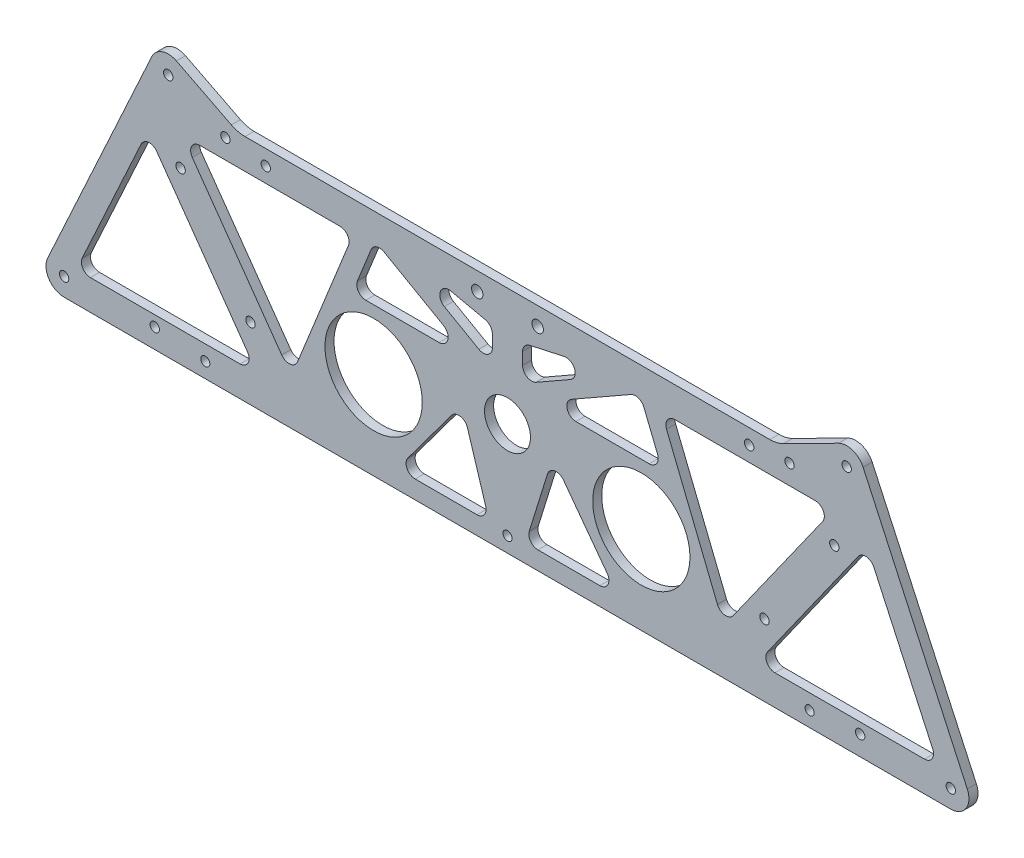
SolidWorks part; units mm, degrees
material "Hexcel AS4C (3000 丝)"
ref_plane "前视基准面" through (0, 0, 0) normal (0, 0, 1) x (1, 0, 0)
ref_plane "上视基准面" through (0, 0, 0) normal (0, 1, 0) x (1, 0, 0)
ref_plane "右视基准面" through (0, 0, 0) normal (1, 0, 0) x (0, 0, -1)
sketch "草图1" plane through (0, 0, 0) normal (0, 0, 1) x (1, 0, 0)
  line L0 (0, 0) -> (102.4311, 23.0839) construction
  line L1 (-1000, 0) -> (49000, 0) construction
  line L2 (29.0129, 77.4629) -> (-5.4514, 2.5065)
  line L3 (0.4406, -5.9838) -> (104.0099, 1.6419)
  line L4 (112.1606, 42.2564) -> (37.1795, 80.3069)
  line L5 (146.7294, -999.9364) -> (146.7294, 49000.0636) construction
  line L6 (0, -6) -> (293.4587, -6)
  line L7 (57.4899, 70) -> (235.9688, 70)
  line L8 (181.2982, 42.2564) -> (256.2792, 80.3069)
  line L9 (293.0182, -5.9838) -> (189.4489, 1.6419)
  line L10 (264.4458, 77.4629) -> (298.9101, 2.5065)
  circle A0 centre (0, 0) radius 1.55
  circle A1 centre (102.4311, 23.0839) radius 16.1
  circle A2 centre (34.4643, 74.9564) radius 1.55
  circle A3 centre (0, 0) radius 6
  circle A4 centre (34.4643, 74.9564) radius 6
  circle A5 centre (102.4311, 23.0839) radius 21.5
  circle A6 centre (191.0276, 23.0839) radius 21.5
  circle A7 centre (258.9944, 74.9564) radius 6
  circle A8 centre (293.4587, 0) radius 6
  circle A9 centre (258.9944, 74.9564) radius 1.55
  circle A10 centre (191.0276, 23.0839) radius 16.1
  circle A11 centre (293.4587, 0) radius 1.55
  circle A12 centre (146.7294, 31) radius 7.6
  point P37 (146.7294, 70)
  point P38 (146.7294, -6)
  dimension "D1" = 3.1
  dimension "D2" = 105
  dimension "D3" = 82.5
  dimension "D4" = 85.5
  dimension "D6" = 45
  dimension "D7" = 3.1
  dimension "D8" = 32.2
  dimension "D9" = 43
  dimension "D12" = 12
  dimension "D13" = 15.2
  dimension "D5" = 12.7
  dimension "D10" = 37
  dimension "D11" = 70
extrude "凸台-拉伸1" add sketch "草图1" along normal blind 3 contours A5 L4 A4 L2 A3 L3 | A4 A2 | A3 A0 | A5 A1 | L6 A8 L9 A6 L8 L7 L4 A5 L3 A3 A12 | A6 A10 | L9 A8 L10 A7 L8 A6 | A7 A9 | A8 A11 region at (46.9003, 31.235, 0) region at (32.5469, 80.4624, 0) region at (1.2466, 5.6955, 0) region at (52.4478, -5.1942, 0) region at (293.2445, -5.8264, 0) region at (120.2355, 34.0144, 0) region at (246.5585, 31.235, 0) region at (201.9582, 40.8882, 0) region at (260.9119, 80.4624, 0)
extrude "凸台-拉伸2" add sketch "草图1<3>" along normal blind 4 from surface contours A4 A2 | A3 A0 | A7 A9 | A8 A11 region at (32.5469, 80.4624, 0) region at (1.2466, 5.6955, 0) region at (293.2445, -5.8264, 0) region at (260.9119, 80.4624, 0) starting at face at (146.7294, 44.9047, 3)
sketch "草图1<3>" plane through (0, 0, 0) normal (0, 0, 1) x (1, 0, 0) same geometry as "草图1"
fillet "圆角1" radius 10 2 edges at (235.9688, 70, 1.5) (57.4899, 70, 1.5)
sketch "草图2" plane through (0, 0, 3) normal (0, 0, 1) x (1, 0, 0)
  line L0 (21.846, 14) -> (38.556, 50.3425) construction
  line L1 (29.0129, 77.4629) -> (-5.4514, 2.5065) construction
  line L2 (0, -6) -> (293.4587, -6) construction
  line L3 (146.7294, -969) -> (146.7294, 49031) construction
  circle A0 centre (38.556, 50.3425) radius 1.55
  circle A1 centre (21.846, 14) radius 1.55 construction
  circle A2 centre (61.6745, 17.7) radius 1.55
  circle A3 centre (231.7842, 17.7) radius 1.55
  circle A4 centre (271.6127, 14) radius 1.55 construction
  circle A5 centre (254.9027, 50.3425) radius 1.55
  circle A8 centre (156.7294, 64) radius 1.9
  circle A9 centre (136.7294, 64) radius 1.9
  dimension "D1" = 3.1
  dimension "D2" = 40
  dimension "D3" = 40
  dimension "D4" = 40
  dimension "D10" = 3.8
  dimension "D11" = 10
  dimension "D12" = 70
  dimension "D5" = 20
  dimension "D6" = 20
extrude "切除-拉伸1" cut sketch "草图2" against normal through all
ref_plane "基准面1" through (146.7294, 0, 0) normal (-1, 0, 0) x (0, 0, 1)
sketch "草图5" plane through (0, 0, 3) normal (0, 0, 1) x (1, 0, 0)
  line L0 (146.7294, -1006.3762) -> (146.7294, 48993.6238) construction
  line L2 (0, -6) -> (293.4587, -6) construction
  line L3 (240.0784, 66.4785) -> (226.7222, 65) construction
  line L5 (59.8821, 70) -> (233.5767, 70) construction
  line L7 (238.102, 71.0825) -> (256.2792, 80.3069) construction
  circle A0 centre (240.0784, 66.4785) radius 1.55
  circle A1 centre (263.4629, 0.5) radius 1.55
  circle A3 centre (293.4587, 0) radius 1.55 construction
  circle A4 centre (29.9958, 0.5) radius 1.55
  circle A5 centre (53.3804, 66.4785) radius 1.55
  circle A6 centre (226.7222, 65) radius 1.55
  circle A7 centre (156.7294, 64) radius 1.9 construction
  circle A8 centre (66.7365, 65) radius 1.55
  point P8 (146.7294, -6)
  dimension "D1" = 3.1
  dimension "D2" = 3.1
  dimension "D3" = 70
  dimension "D4" = 6.5
  dimension "D5" = 30
  dimension "D6" = 5
  dimension "D7" = 70
  dimension "D8" = 5
extrude "切除-拉伸3" cut sketch "草图5" against normal through all
sketch "草图6" plane through (0, 0, 3) normal (0, 0, 1) x (1, 0, 0)
  circle A0 centre (0, 0) radius 300
  dimension "D1" = 600
extrude "切除-拉伸4" cut sketch "草图6" along normal through all
sketch "草图7" plane through (0, 0, 3) normal (0, 0, 1) x (1, 0, 0)
  line L0 (0, -6) -> (293.4587, -6) construction
  line L1 (146.7294, -969) -> (146.7294, 49031) construction
  circle A0 centre (146.7294, -1) radius 1.5
  circle A1 centre (246.7294, -1) radius 1.5
  circle A2 centre (46.7294, -1) radius 1.5
  dimension "D1" = 3
  dimension "D2" = 5
  dimension "D4" = 100
  dimension "D3" = 2
extrude "切除-拉伸5" cut sketch "草图7" against normal through all
sketch "草图8" plane through (0, 0, 3) normal (0, 0, 1) x (1, 0, 0)
  line L0 (27.6533, 55.3555) -> (4.0404, 4)
  line L1 (4.0404, 4) -> (64.025, 4)
  line L2 (64.025, 4) -> (27.6533, 55.3555)
  line L3 (39.0686, 60) -> (75.1886, 9)
  line L4 (146.7294, -1001) -> (146.7294, 48999) construction
  line L5 (75.1886, 9) -> (95.7505, 60)
  line L6 (95.7505, 60) -> (39.0686, 60)
  line L7 (102.8781, 61.633) -> (95.3996, 43.0839)
  line L8 (95.3996, 43.0839) -> (135.3996, 43.0839)
  line L9 (135.3996, 43.0839) -> (102.8781, 61.633)
  line L10 (29.0129, 77.4629) -> (-5.4514, 2.5065) construction
  line L11 (0, -6) -> (293.4587, -6) construction
  line L12 (38.556, 50.3425) -> (61.6745, 17.7) construction
  line L13 (59.8821, 70) -> (233.5767, 70) construction
  line L14 (108.7294, 64) -> (141.7294, 45.1779)
  line L15 (141.7294, 45.1779) -> (141.7294, 56.7604)
  line L16 (141.7294, 56.7604) -> (108.7294, 64)
  line L17 (131.7294, 29) -> (110.2046, 0)
  line L18 (110.2046, 0) -> (140.7294, 0)
  line L19 (140.7294, 0) -> (131.7294, 29)
  line L20 (152.7294, 0) -> (161.7294, 29)
  line L21 (183.2541, 0) -> (152.7294, 0)
  line L22 (161.7294, 29) -> (183.2541, 0)
  line L23 (151.7294, 56.7604) -> (184.7294, 64)
  line L24 (151.7294, 45.1779) -> (151.7294, 56.7604)
  line L25 (184.7294, 64) -> (151.7294, 45.1779)
  line L26 (158.0592, 43.0839) -> (190.5806, 61.633)
  line L27 (198.0592, 43.0839) -> (158.0592, 43.0839)
  line L28 (190.5806, 61.633) -> (198.0592, 43.0839)
  line L29 (197.7083, 60) -> (254.3901, 60)
  line L30 (218.2702, 9) -> (197.7083, 60)
  line L31 (254.3901, 60) -> (218.2702, 9)
  line L32 (229.4338, 4) -> (265.8055, 55.3555)
  line L33 (289.4183, 4) -> (229.4338, 4)
  line L34 (265.8055, 55.3555) -> (289.4183, 4)
  circle A1 centre (102.4311, 23.0839) radius 16.1 construction
  circle A2 centre (136.7294, 64) radius 1.9 construction
  dimension "D1" = 10
  dimension "D2" = 8
  dimension "D3" = 6
  dimension "D4" = 6
  dimension "D5" = 10
  dimension "D6" = 15
  dimension "D7" = 20
  dimension "D8" = 6
  dimension "D9" = 20
  dimension "D10" = 40
  dimension "D11" = 20
  dimension "D12" = 38
  dimension "D13" = 6
  dimension "D14" = 6
  dimension "D15" = 5
  dimension "D16" = 15
  dimension "D17" = 35
  dimension "D18" = 6
  dimension "D19" = 20
extrude "切除-拉伸6" cut sketch "草图8" against normal through all
fillet "圆角2" radius 3 30 edges at (4.0404, 4, 1.5) (27.6533, 55.3555, 1.5) (64.025, 4, 1.5) (265.8055, 55.3555, 1.5) (289.4183, 4, 1.5) (229.4338, 4, 1.5) (161.7294, 29, 1.5) (183.2541, 0, 1.5) (152.7294, 0, 1.5) (184.7294, 64, 1.5) (151.7294, 45.1779, 1.5) (151.7294, 56.7604, 1.5) (254.3901, 60, 1.5) (218.2702, 9, 1.5) (197.7083, 60, 1.5) (190.5806, 61.633, 1.5) (198.0592, 43.0839, 1.5) (158.0592, 43.0839, 1.5) (95.3996, 43.0839, 1.5) (102.8781, 61.633, 1.5) (135.3996, 43.0839, 1.5) (75.1886, 9, 1.5) (39.0686, 60, 1.5) (141.7294, 45.1779, 1.5) (108.7294, 64, 1.5) (141.7294, 56.7604, 1.5) (110.2046, 0, 1.5) (131.7294, 29, 1.5) (140.7294, 0, 1.5) (95.7505, 60, 1.5)
